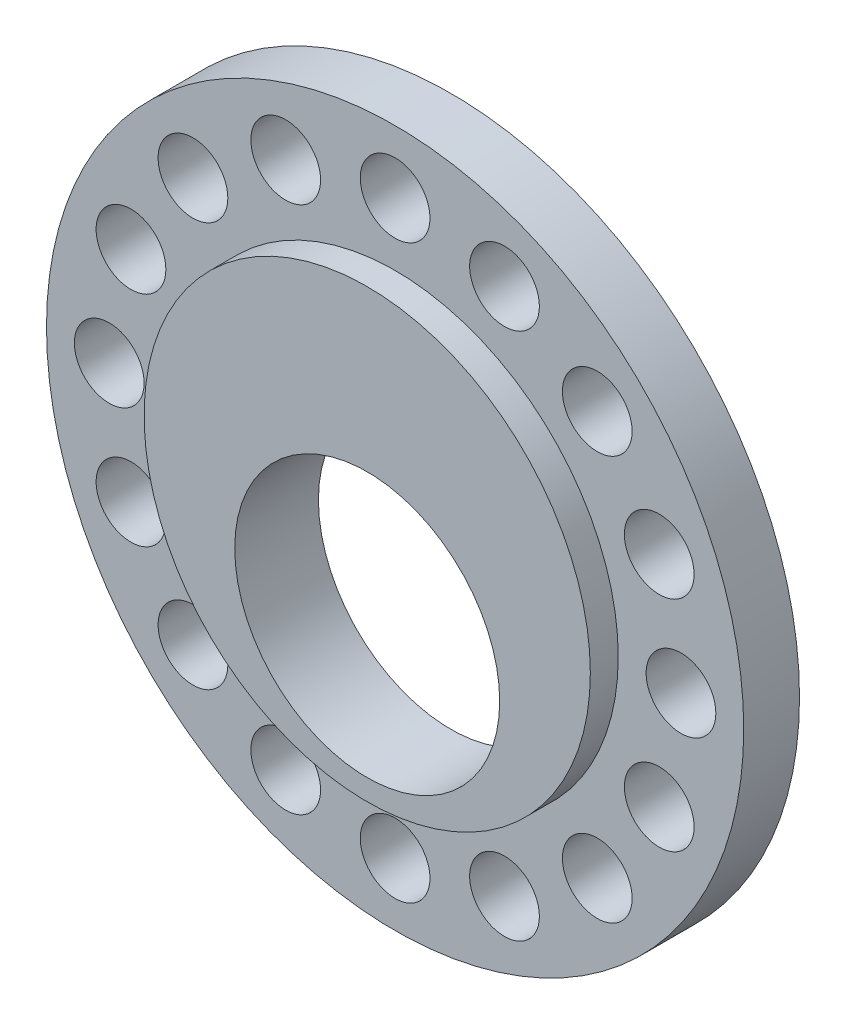
SolidWorks part; units mm, degrees
ref_plane "Front Plane" through (0, 0, 0) normal (1, 0, 0) x (0, 1, 0)
ref_plane "Top Plane" through (0, 0, 0) normal (0, 0, 1) x (0, 1, 0)
ref_plane "Right Plane" through (0, 0, 0) normal (0, 1, 0) x (-1, 0, 0)
sketch "Sketch1" plane through (0, 0, 0) normal (0, 0, 1) x (0, 1, 0)
  line L0 (0, 0) -> (-5, 0) construction
  line L1 (0, 16) -> (0, 20.5) construction
  circle A0 centre (0, 0) radius 16
  circle A1 centre (-5, 0) radius 9.5
  circle A2 centre (0, 0) radius 25
  circle A3 centre (0, 20.5) radius 2.5
  circle A4 centre (7.845, 18.9395) radius 2.5
  circle A5 centre (14.4957, 14.4957) radius 2.5
  circle A6 centre (18.9395, 7.845) radius 2.5
  circle A7 centre (20.5, 0) radius 2.5
  circle A8 centre (18.9395, -7.845) radius 2.5
  circle A9 centre (14.4957, -14.4957) radius 2.5
  circle A10 centre (7.845, -18.9395) radius 2.5
  circle A11 centre (0, -20.5) radius 2.5
  circle A12 centre (-7.845, -18.9395) radius 2.5
  circle A13 centre (-14.4957, -14.4957) radius 2.5
  circle A14 centre (-18.9395, -7.845) radius 2.5
  circle A15 centre (-20.5, 0) radius 2.5
  circle A16 centre (-18.9395, 7.845) radius 2.5
  circle A17 centre (-14.4957, 14.4957) radius 2.5
  circle A18 centre (-7.845, 18.9395) radius 2.5
  point P42 (0, 0)
  dimension "D2" = 19
  dimension "D3" = 32
  dimension "D4" = 50
  dimension "D6" = 5
  dimension "D1" = 5
  dimension "D5" = 4.5
  dimension "D7" = 16
extrude "Boss-Extrude1" add sketch "Sketch1" along normal blind 6 contours A0 A1 region at (0, -15.5475, 0)
extrude "Boss-Extrude2" add sketch "Sketch1<3>" along normal blind 4 contours A2 A18 A17 A16 A15 A14 A13 A12 A11 A10 A9 A8 A7 A6 A5 A4 A3 A0 region at (0, -24.2929, 0)
sketch "Sketch1<3>" plane through (0, 0, 0) normal (0, 0, 1) x (0, 1, 0) same geometry as "Sketch1"
fillet "Fillet1" [suppressed] radius 1
chamfer "Chamfer1" [suppressed] distance 0.5 angle 45
sketch "Sketch2" [suppressed] plane through (0, 0, 0) normal (1, 0, 0) x (0, 1, 0)
  line L0 (-24.5, 0) -> (24.5, 0) construction
  line L1 (-24.5, 0) -> (24.5, 0)
  line L2 (0, 0) -> (0, 3) construction
  line L3 (0, 3) -> (-5, 3) construction
  dimension "D1" = 5
  dimension "D2" = 3
